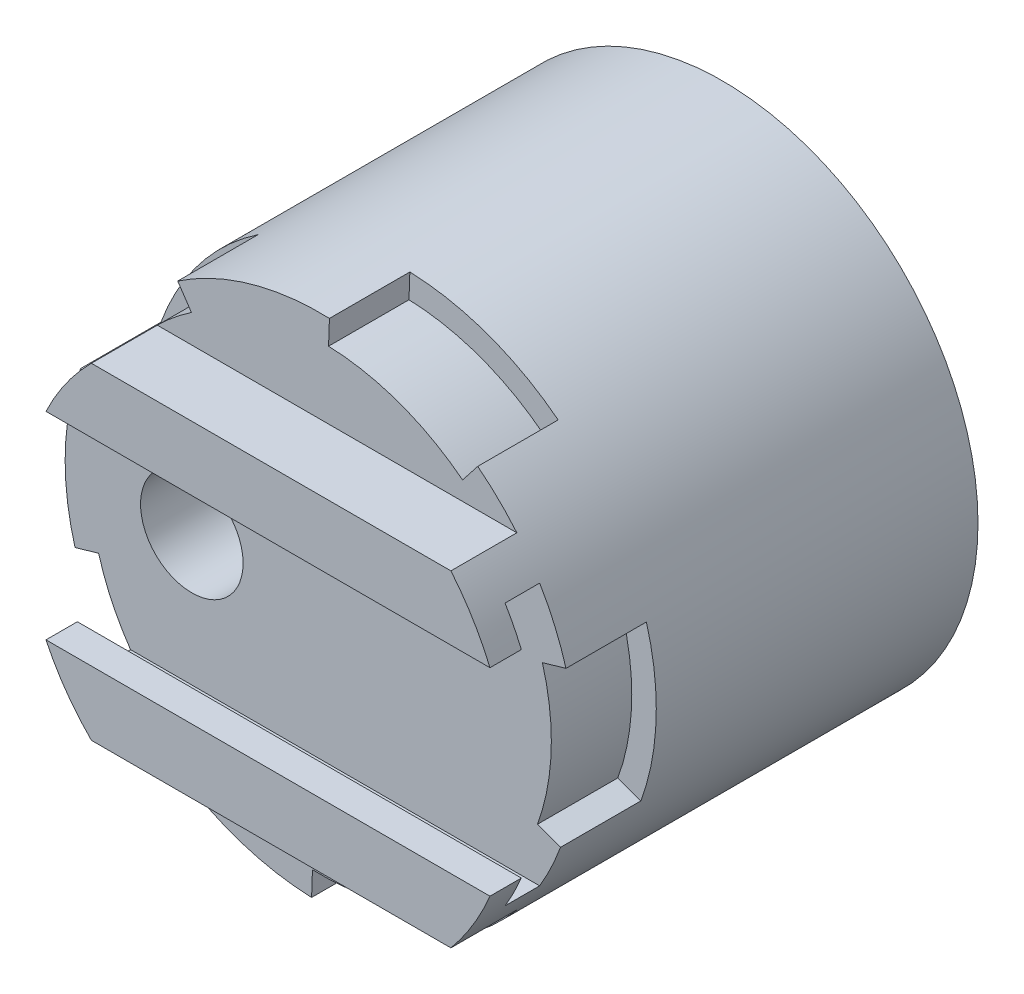
SolidWorks part; units mm, degrees
ref_plane "Front Plane" through (0, 0, 0) normal (0, 0, 1) x (1, 0, 0)
ref_plane "Top Plane" through (0, 0, 0) normal (0, 1, 0) x (1, 0, 0)
ref_plane "Right Plane" through (0, 0, 0) normal (1, 0, 0) x (0, 0, -1)
sketch "Sketch1" plane through (0, 0, 0) normal (0, 0, 1) x (1, 0, 0)
  circle A0 centre (0, 0) radius 31.75
  circle A1 centre (0, 0) radius 28.7
  dimension "D1" = 63.5
  dimension "D2" = 3.05
extrude "Boss-Extrude1" add sketch "Sketch1" along normal blind 50 contours A1 region at (0, 0, 0)
extrude "Boss-Extrude2" add sketch "Sketch1<3>" along normal blind 40
sketch "Sketch1<3>" plane through (0, 0, 0) normal (0, 0, 1) x (1, 0, 0) same geometry as "Sketch1"
sketch "Sketch3" plane through (0, 0, 0) normal (0, 0, -1) x (-1, 0, 0)
  circle A0 centre (16, 0) radius 6.375
  circle A1 centre (16, 0) radius 15.5
  dimension "D1" = 12.75
  dimension "D3" = 31
  dimension "D2" = 16
extrude "Cut-Extrude1" cut sketch "Sketch3" against normal up to surface (50 mm away) contours A0 up to face at (28.7, 0, 50)
extrude "Cut-Extrude2" cut sketch "Sketch3<3>" against normal offset from surface (25 mm away) 15 contours A1 A0 region at (-0.9384, 0, 0) up to face at (31.75, 0, 40)
sketch "Sketch3<3>" plane through (0, 0, 0) normal (0, 0, -1) x (-1, 0, 0) same geometry as "Sketch3"
sketch "Sketch4" plane through (0, 0, 50) normal (0, 0, 1) x (1, 0, 0)
  line L0 (0, 0) -> (-31.75, 0) construction
  line L1 (1.1081, 31.7307) -> (-1.1081, -31.7307)
  line L2 (-29.8352, 10.8591) -> (29.8352, -10.8591)
  line L3 (30.5201, 8.7515) -> (-30.5201, -8.7515)
  line L4 (17.7544, -26.3219) -> (-17.7544, 26.3219)
  line L5 (-19.5473, -25.0193) -> (19.5473, 25.0193)
  circle A0 centre (0, 0) radius 28.7 construction
  circle A1 centre (0, 0) radius 31.75 construction
  circle A2 centre (0, 0) radius 28.7
  circle A3 centre (0, 0) radius 31.75
  point P19 (0, 0)
  circle M4 centre (0, 0) radius 28.7
  dimension "D1" = 5
  dimension "D2" = 20
extrude "Boss-Extrude3" add sketch "Sketch4" against normal up to next contours A2 L0 A3 L3 | L0 L2 A3 M4 | L1 A3 L4 M4 | L3 A3 L5 M4 | L4 A3 L2 M4 | L5 A3 L1 M4 region at (-29.859, -4.1964, 50) region at (-29.6401, 5.2263, 50) region at (-8.2017, 28.6028, 50) region at (-10.177, -27.961, 50) region at (23.4476, -18.3193, 50) region at (24.6684, 16.6391, 50)
ref_plane "Plane1" through (0, 0, 50) normal (0, 0, 1) x (1, 0, 0)
sketch "Sketch7" plane through (0, 0, 50) normal (0, 0, 1) x (1, 0, 0)
  line L10 (-17.6695, -22.6159) -> (-19.5473, -25.0193)
  line L11 (-1.1081, -31.7307) -> (-1.0016, -28.6825)
  line L12 (16.0488, -23.7934) -> (17.7544, -26.3219)
  line L13 (29.8352, -10.8591) -> (26.9692, -9.816)
  line L14 (27.5882, 7.9108) -> (30.5201, 8.7515)
  line L15 (19.5473, 25.0193) -> (17.6695, 22.6159)
  line L16 (1.0016, 28.6825) -> (1.1081, 31.7307)
  line L17 (-17.7544, 26.3219) -> (-16.0488, 23.7934)
  line L18 (-26.9692, 9.816) -> (-29.8352, 10.8591)
  line L19 (-30.5201, -8.7515) -> (-27.5882, -7.9108)
  line L20 (-17.6695, -22.6159) -> (-19.5473, -25.0193)
  line L21 (-1.1081, -31.7307) -> (-1.0016, -28.6825)
  line L22 (16.0488, -23.7934) -> (17.7544, -26.3219)
  line L23 (29.8352, -10.8591) -> (26.9692, -9.816)
  line L24 (27.5882, 7.9108) -> (30.5201, 8.7515)
  line L25 (19.5473, 25.0193) -> (17.6695, 22.6159)
  line L26 (1.0016, 28.6825) -> (1.1081, 31.7307)
  line L27 (-17.7544, 26.3219) -> (-16.0488, 23.7934)
  line L28 (-26.9692, 9.816) -> (-29.8352, 10.8591)
  line L29 (-30.5201, -8.7515) -> (-27.5882, -7.9108)
  arc A10 (-27.5882, -7.9108) -> (-17.6695, -22.6159) centre (0, 0) ccw
  arc A11 (-19.5473, -25.0193) -> (-1.1081, -31.7307) centre (0, 0) ccw
  arc A12 (-1.0016, -28.6825) -> (16.0488, -23.7934) centre (0, 0) ccw
  arc A13 (17.7544, -26.3219) -> (29.8352, -10.8591) centre (0, 0) ccw
  arc A14 (26.9692, -9.816) -> (27.5882, 7.9108) centre (0, 0) ccw
  arc A15 (30.5201, 8.7515) -> (19.5473, 25.0193) centre (0, 0) ccw
  arc A16 (17.6695, 22.6159) -> (1.0016, 28.6825) centre (0, 0) ccw
  arc A17 (1.1081, 31.7307) -> (-17.7544, 26.3219) centre (0, 0) ccw
  arc A18 (-16.0488, 23.7934) -> (-26.9692, 9.816) centre (0, 0) ccw
  arc A19 (-29.8352, 10.8591) -> (-30.5201, -8.7515) centre (0, 0) ccw
  arc A20 (-27.5882, -7.9108) -> (-17.6695, -22.6159) centre (0, 0) ccw
  arc A21 (-19.5473, -25.0193) -> (-1.1081, -31.7307) centre (0, 0) ccw
  arc A22 (-1.0016, -28.6825) -> (16.0488, -23.7934) centre (0, 0) ccw
  arc A23 (17.7544, -26.3219) -> (29.8352, -10.8591) centre (0, 0) ccw
  arc A24 (26.9692, -9.816) -> (27.5882, 7.9108) centre (0, 0) ccw
  arc A25 (30.5201, 8.7515) -> (19.5473, 25.0193) centre (0, 0) ccw
  arc A26 (17.6695, 22.6159) -> (1.0016, 28.6825) centre (0, 0) ccw
  arc A27 (1.1081, 31.7307) -> (-17.7544, 26.3219) centre (0, 0) ccw
  arc A28 (-16.0488, 23.7934) -> (-26.9692, 9.816) centre (0, 0) ccw
  arc A29 (-29.8352, 10.8591) -> (-30.5201, -8.7515) centre (0, 0) ccw
  dimension "D1" = 0
sketch "Sketch5" plane through (0, 0, 0) normal (1, 0, 0) x (0, 0, -1)
  line L27 (-54, -16) -> (-50, -16) construction
  line L28 (-58.5, -12) -> (-54, -12) construction
  line L29 (-54, -16) -> (-54, -12) construction
  line L45 (-54, -16) -> (-50, -16) construction
  line L46 (-58.5, -12) -> (-54, -12) construction
  line L47 (-54, -16) -> (-54, -12) construction
  line L48 (-58.2, -12.3) -> (-54.3, -12.3)
  line L49 (-54.3, -12.3) -> (-54.3, -16.3)
  line L50 (-54.3, -16.3) -> (-50, -16.3)
  line L51 (-50, -16.3) -> (-50, -20.3)
  line L52 (-50, -20.3) -> (-58.2, -20.3)
  line L53 (-58.2, -20.3) -> (-58.2, -12.3)
  dimension "D1" = 0.3
  dimension "D2" = 0.3
  dimension "D3" = 0.3
  dimension "D4" = 0.3
  dimension "D5" = 4
extrude "Boss-Extrude4" add sketch "Sketch5" along normal blind 30 and the other way blind 30
mirror "Mirror1" about plane through (0, 0, 0) normal (0, 1, 0) of "Boss-Extrude4"
extrude "Cut-Extrude3" cut sketch "Sketch7" along normal through all flip side to cut
ref_plane "Plane2" through (-9.625, 0, 0) normal (-1, 0, 0) x (0, 0, 1)
